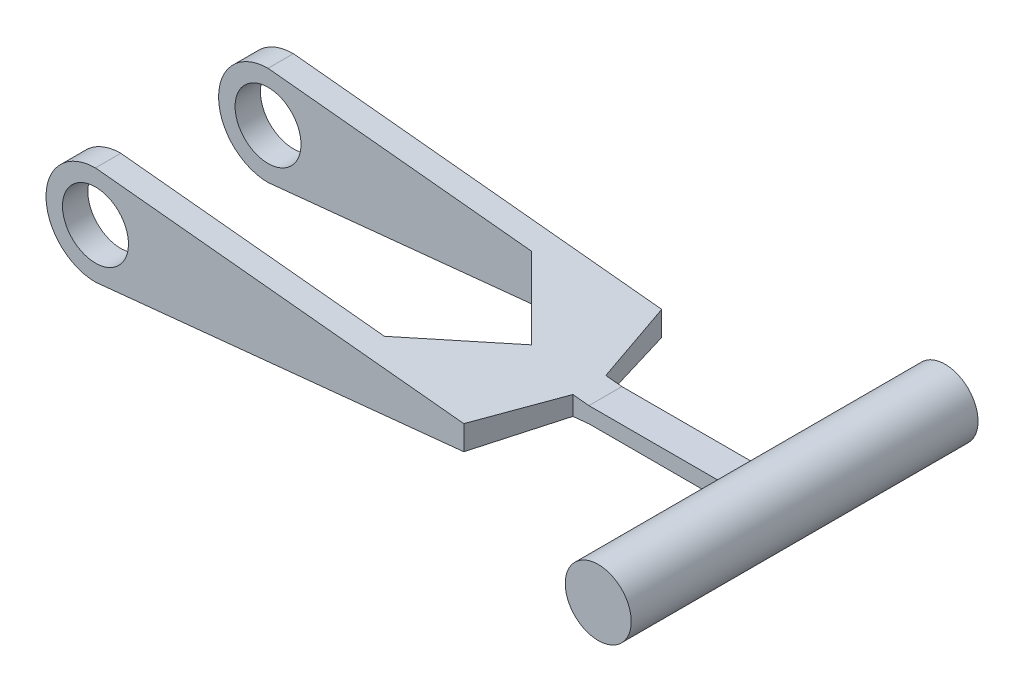
SolidWorks part; units mm, degrees
ref_plane "Front Plane" through (0, 0, 0) normal (0, 0, 1) x (1, 0, 0)
ref_plane "Top Plane" through (0, 0, 0) normal (0, 1, 0) x (1, 0, 0)
ref_plane "Right Plane" through (0, 0, 0) normal (1, 0, 0) x (0, 0, -1)
sketch "Sketch1" plane through (0, 0, 0) normal (0, 0, 1) x (1, 0, 0)
  line L0 (-85, 15) -> (39.5992, 2.3846)
  line L1 (100, -15) -> (-85, -15)
  line L2 (100, -15) -> (100, 15)
  line L3 (100, 15) -> (-85, 15)
  line L5 (100, -15) -> (-91.1646, 13.6747) construction
  line L6 (100, 15) -> (-91.1646, -13.6747) construction
  line L7 (39.5992, 2.3846) -> (66.3595, 2.3846)
  line L8 (0, 0) -> (68.8595, 0) construction
  line L9 (66.3595, 2.3846) -> (80.373, 2.3846)
  line L10 (-85, -15) -> (39.5992, -2.3846)
  line L11 (39.5992, 0) -> (39.5992, 2.3846) construction
  line L12 (39.5992, 0) -> (39.5992, -2.3846) construction
  line L13 (39.5992, -2.3846) -> (80.2152, -2.3846)
  circle A0 centre (-85, 0) radius 15
  circle A1 centre (-85, 0) radius 10
  circle A2 centre (90, -0.3211) radius 10
  point P0 (0, 0)
  dimension "D2" = 30
  dimension "D3" = 20
extrude "Boss-Extrude1" add sketch "Sketch1" along normal blind 60 contours L0 A0 L10 A1 | A2 L9 L7 L0 A0 L10 L13 | A2 region at (-83.5394, 14.4257, 0) region at (-21.1784, 0.0001, 0) region at (90, -0.3211, 0)
sketch "Sketch2" plane through (0, 2.3846, 0) normal (0, 1, 0) x (1, 0, 0)
  line L0 (26.6666, 0) -> (-100, 0)
  line L1 (-100, 0) -> (-100, -7.6838)
  line L2 (-100, 0) -> (-100, -60) construction
  line L3 (-100, -7.6838) -> (-5.087, -7.6838)
  line L4 (-5.087, -7.6838) -> (-5.087, -30) construction
  line L5 (17.2292, -30) -> (-126.2365, -30) construction
  line L6 (-126.2365, -30) -> (17.2292, -30) construction
  line L7 (-5.087, -52.3162) -> (-100, -52.3162)
  line L8 (-100, -52.3162) -> (-100, -60)
  line L9 (-100, -60) -> (26.6666, -60)
  line L11 (80.373, -25) -> (80.373, -3.7126)
  line L12 (80.373, -35) -> (80.373, -56.2874)
  line L14 (26.6666, 0) -> (34.7347, -25)
  line L15 (34.7347, -25) -> (80.373, -25)
  line L16 (80.373, -60) -> (80.373, 0) construction
  line L17 (34.7347, -25) -> (34.7347, -30) construction
  line L18 (34.7347, -30) -> (34.7347, -35) construction
  line L19 (26.6666, -60) -> (34.7347, -35)
  line L20 (34.7347, -35) -> (80.373, -35)
  line L21 (80.373, -35) -> (80.373, -25)
  line L22 (-5.087, -7.6838) -> (17.2292, -30)
  line L23 (17.2292, -30) -> (-5.087, -52.3162)
  line L24 (34.7347, -30) -> (126.9195, -30) construction
  line L25 (-5.087, -30) -> (-5.087, -52.3162) construction
  line L26 (-5.087, -7.6838) -> (-5.087, 0) construction
  line L27 (-5.087, -52.3162) -> (-5.087, -60) construction
  line L28 (80.373, -3.7126) -> (100, -3.7126)
  line L29 (100, -60) -> (100, 0) construction
  line L30 (100, -3.7126) -> (100, -56.2874)
  line L31 (100, -56.2874) -> (80.373, -56.2874)
  line L32 (80.373, -56.2874) -> (80.373, -35)
  line M13 (39.5992, 0) -> (39.5992, -60)
  line M15 (80.373, -60) -> (80.373, 0)
  dimension "D1" = 52.5749
  dimension "D2" = 5
extrude "Cut-Extrude1" cut sketch "Sketch2" against normal mid plane 40 flip side to cut contours L22 L23 L7 L8 L9 L19 L20 L15 L14 L0 L1 L3 M13 | L20 L15 M13 M15 | L31 L30 L28 M15 region at (29.2546, 2.3846, 12.9667) region at (59.9861, 2.3846, 30) region at (90.1865, 2.3846, 30)
sketch "Sketch3" plane through (0, 0, 56.2874) normal (0, 0, 1) x (1, 0, 0)
  circle A0 centre (90, -0.3211) radius 10
extrude "Boss-Extrude2" add sketch "Sketch3" along normal blind 26.2874
sketch "Sketch4" plane through (0, 0, 3.7126) normal (0, 0, -1) x (-1, 0, 0)
  circle A0 centre (-90, -0.3211) radius 10
extrude "Boss-Extrude3" add sketch "Sketch4" along normal blind 26.2874
